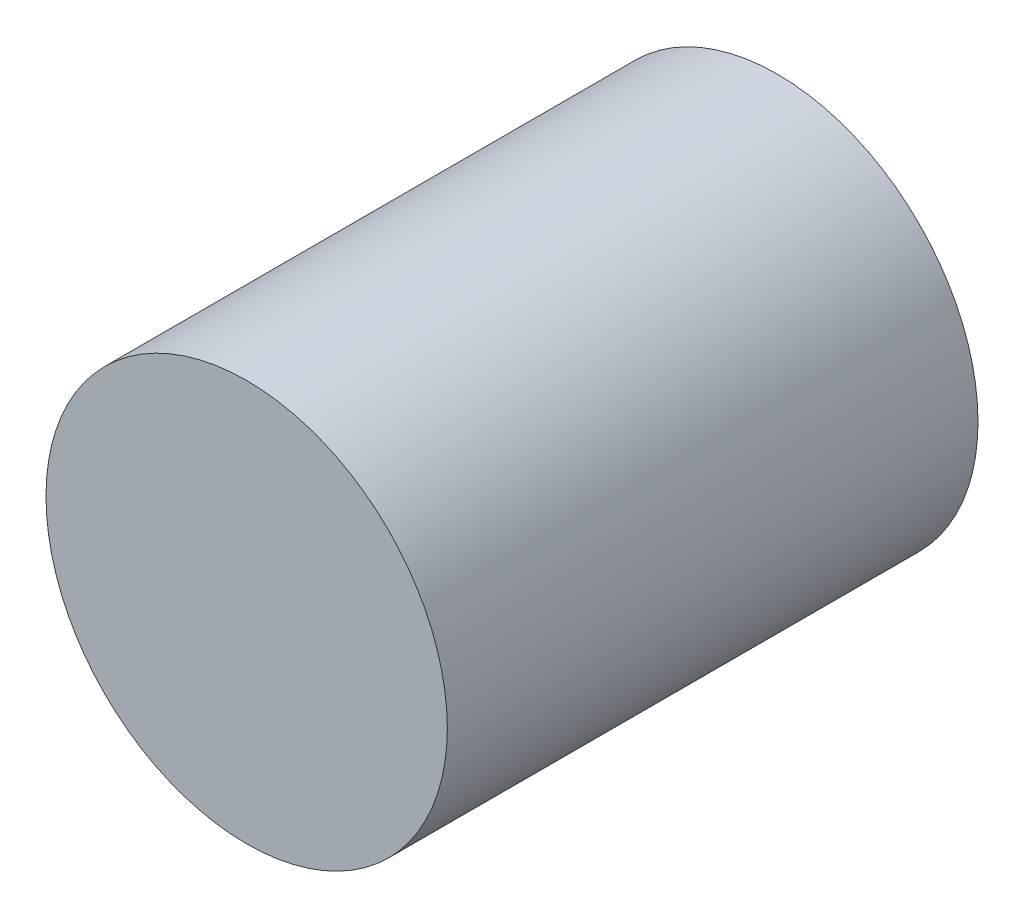
SolidWorks part; units mm, degrees
material "Aço"
ref_plane "Plano superior" through (0, 0, 0) normal (0, 0, 1) x (1, 0, 0)
ref_plane "Plano frontal" through (0, 0, 0) normal (0, 1, 0) x (1, 0, 0)
ref_plane "Plano direito" through (0, 0, 0) normal (1, 0, 0) x (0, 0, -1)
other "Caixa delimitadora"
ref_plane "Default Plane" through (-78.1989, -63.94, 0) normal (0, 1, 0) x (1, 0, 0)
sketch "Esboço1" plane through (0, 0, 0) normal (0, 0, 1) x (1, 0, 0)
  line L1 (-78.1989, -63.755) -> (78.1989, -63.755) construction
  line L2 (-78.1989, -63.755) -> (-78.1989, 63.755) construction
  line L3 (-78.1989, 63.755) -> (78.1989, 63.755) construction
  line L4 (78.1989, -63.755) -> (78.1989, 63.755) construction
  line L5 (-78.1989, -63.755) -> (78.1989, 63.755) construction
  line L6 (-78.1989, 63.755) -> (78.1989, -63.755) construction
  circle A0 centre (0, 0) radius 15.125
  point P0 (0, 0)
  dimension "D3" = 30.25
  dimension "D1" = 156.3979
  dimension "D2" = 127.51
extrude "Ressalto-extrusão1" add sketch "Esboço1" along normal blind 40
